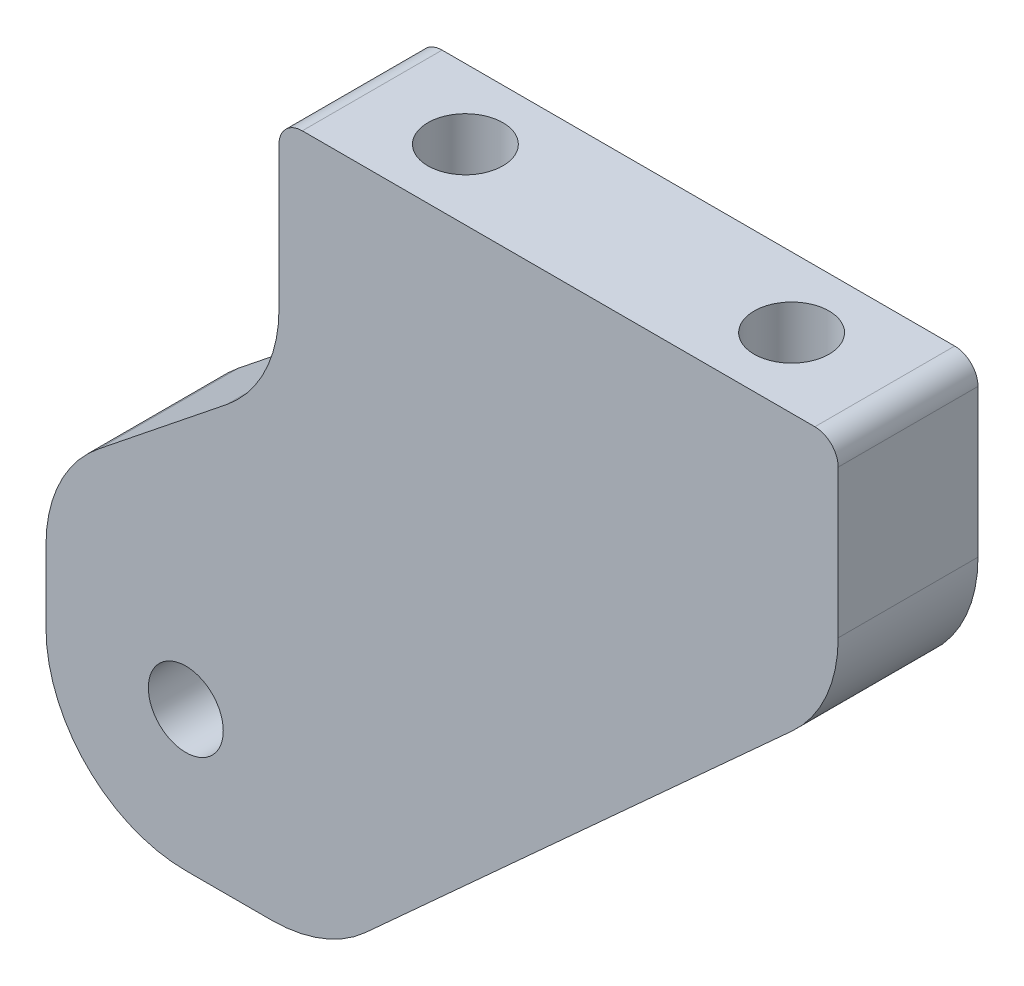
SolidWorks part; units mm, degrees
material "SS 304 (Default)"
ref_plane "Front Plane" through (0, 0, 0) normal (0, 0, 1) x (1, 0, 0)
ref_plane "Top Plane" through (0, 0, 0) normal (0, 1, 0) x (1, 0, 0)
ref_plane "Right Plane" through (0, 0, 0) normal (1, 0, 0) x (0, 0, -1)
sketch "Sketch1" plane through (0, 0, 0) normal (0, 0, 1) x (1, 0, 0)
  line L1 (26.9875, 23.8125) -> (-26.9875, 23.8125)
  line L2 (26.9875, 23.8125) -> (26.9875, -23.8125)
  line L3 (26.9875, -23.8125) -> (-26.9875, -23.8125)
  line L4 (-26.9875, 23.8125) -> (-26.9875, -23.8125)
  line L5 (26.9875, 23.8125) -> (-26.9875, -23.8125) construction
  line L6 (26.9875, -23.8125) -> (-26.9875, 23.8125) construction
  point P0 (0, 0)
  dimension "D1" = 53.975
  dimension "D2" = 47.625
sheet metal parameters "Sheet-Metal1" thickness 9.525 parameters "D1"=8.7312
base flange "Base-Flange1" sketch "Sketch1" thickness 9.525 reverse thickness direction yes parameters "D1"=8.7312
hole_wizard "1/4-20 Tapped Hole1" positions "Sketch2" profile "Sketch3" tap size "1/4-20" standard "ANSI Inch"
sketch "Sketch2" plane through (0, 23.8125, 0) normal (0, 1, 0) x (1, 0, 0)
  line L0 (-3.175, -4.7625) -> (-26.9875, -4.7625) construction
  line L1 (-26.9875, -9.525) -> (-26.9875, 0) construction
  line L3 (26.9875, -9.525) -> (26.9875, 0) construction
  point P0 (-3.175, -4.7625)
  point P2 (19.05, -4.7625)
  dimension "D1" = 22.225
  dimension "D2" = 7.9375
sketch "Sketch3" plane through (-3.175, 23.8125, 4.7625) normal (1, 0, 0) x (0, 0, 1)
  line L0 (0, 0) -> (0, 20.5838)
  line L1 (0, 20.5838) -> (2.5527, 19.05)
  line L2 (2.5527, 19.05) -> (2.5527, 0)
  line L5 (2.5527, 0) -> (0, 0)
  line L10 (0, 20.5838) -> (-2.5527, 19.05) construction
  line L11 (0, -6.35) -> (0, 107.95) construction
  dimension "Tap Drill Dia." = 5.1054
  dimension "Tap Drill Depth" = 19.05
  dimension "Drill Angle" = 118
cosmetic thread "Hole Thread1" parameters "D1"=12.7, "D2"=6.35
cosmetic thread "Hole Thread2" parameters "D1"=12.7, "D2"=6.35
sketch "Sketch4" plane through (0, 0, 0) normal (0, 0, -1) x (-1, 0, 0)
  line L0 (17.4625, -14.224) -> (17.4625, -14.351) construction
  line L1 (17.5895, -14.224) -> (17.5895, -14.351)
  line L2 (17.3355, -14.224) -> (17.3355, -14.351)
  line L4 (26.9875, 23.8125) -> (26.9875, -23.8125) construction
  line L5 (-26.9875, 23.8125) -> (26.9875, 23.8125) construction
  arc A0 (17.5895, -14.224) -> (17.3355, -14.224) centre (17.4625, -14.224) ccw
  arc A1 (17.3355, -14.351) -> (17.5895, -14.351) centre (17.4625, -14.351) ccw
  point P3 (17.4625, -14.2875)
  dimension "D3" = 0.127
  dimension "D1" = 38.1
  dimension "D2" = 0.127
  dimension "D4" = 9.525
extrude "Cut-Extrude1" cut sketch "Sketch4" against normal through all
sketch "Sketch5" plane through (0, 0, 9.525) normal (0, 0, 1) x (1, 0, 0)
  line L2 (-26.9875, -23.8125) -> (26.9875, -23.8125) construction
  line L5 (26.9875, -23.8125) -> (26.9875, 7.9375)
  line L6 (26.9875, -23.8125) -> (26.9875, 23.8125) construction
  line L7 (26.9875, 7.9375) -> (-7.9375, -23.8125)
  line L8 (-7.9375, -23.8125) -> (26.9875, -23.8125)
  line L9 (26.9875, 23.8125) -> (-26.9875, 23.8125) construction
  arc A0 (-17.5895, -14.351) -> (-17.3355, -14.351) centre (-17.4625, -14.351) ccw construction
  dimension "D1" = 15.875
  dimension "D2" = 9.525
extrude "Cut-Extrude2" cut sketch "Sketch5" against normal up to next
hole_wizard "1/4-20 Tapped Hole2" positions "Sketch6" profile "Sketch7" tap size "1/4-20" standard "ANSI Inch" end condition up to next
sketch "Sketch6" plane through (0, 0, 9.525) normal (0, 0, 1) x (1, 0, 0)
  line L0 (26.9875, 23.8125) -> (-26.9875, 23.8125) construction
  line L1 (-26.9875, 23.8125) -> (-26.9875, -23.8125) construction
  point P0 (-17.4625, -14.2875)
  dimension "D1" = 38.1
  dimension "D2" = 9.525
sketch "Sketch7" plane through (-17.4625, -14.2875, 9.525) normal (1, 0, 0) x (0, -1, 0)
  line L0 (0, 0) -> (0, 9.525)
  line L1 (0, 9.525) -> (2.5527, 9.525)
  line L2 (2.5527, 9.525) -> (2.5527, 0)
  line L5 (2.5527, 0) -> (0, 0)
  line L11 (0, -6.35) -> (0, 107.95) construction
  dimension "Thru Tap Drill Dia." = 5.1054
  dimension "Thru Tap Drill Depth" = 9.525
cosmetic thread "Hole Thread3" parameters "D2"=6.35
sketch "Sketch8" plane through (0, 0, 9.525) normal (0, 0, 1) x (1, 0, 0)
  line L0 (-26.9875, -4.7625) -> (-11.1125, 7.9375)
  line L1 (-26.9875, 23.8125) -> (-26.9875, -23.8125) construction
  line L2 (-11.1125, 7.9375) -> (-11.1125, 23.8125)
  line L3 (26.9875, 23.8125) -> (-26.9875, 23.8125) construction
  line L4 (-11.1125, 23.8125) -> (-26.9875, 23.8125)
  line L5 (-26.9875, 23.8125) -> (-26.9875, -4.7625)
  line L6 (26.9875, 7.9375) -> (26.9875, 23.8125) construction
  line L7 (-26.9875, -23.8125) -> (-7.9375, -23.8125) construction
  dimension "D1" = 38.1
  dimension "D2" = 15.875
  dimension "D3" = 19.05
extrude "Cut-Extrude3" cut sketch "Sketch8" against normal up to next normal cut yes
fillet "Fillet2" radius 1.5875 2 edges at (26.9875, 23.8125, 4.7625) (-11.1125, 23.8125, 4.7625)
fillet "Fillet1" radius 9.525 5 edges at (26.9875, 7.9375, 4.7625) (-7.9375, -23.8125, 4.7625) (-26.9875, -23.8125, 4.7625) (-11.1125, 7.9375, 4.7625) (-26.9875, -4.7625, 4.7625)
flat pattern "Flat-Pattern1" [suppressed]
sketch "Bend-Lines1" plane through (0, 0, 0) normal (0, 1, 0) x (-1, 0, 0)
sketch3d "Bounding-Box1" [suppressed]
  line L0 (38.1, 0, 0) -> (38.1, 47.625, 0) construction
  line L1 (0, 0, 0) -> (0, 47.625, 0) construction
  line L2 (38.1, 0, 0) -> (0, 0, 0) construction
  line L3 (38.1, 47.625, 0) -> (0, 47.625, 0) construction
